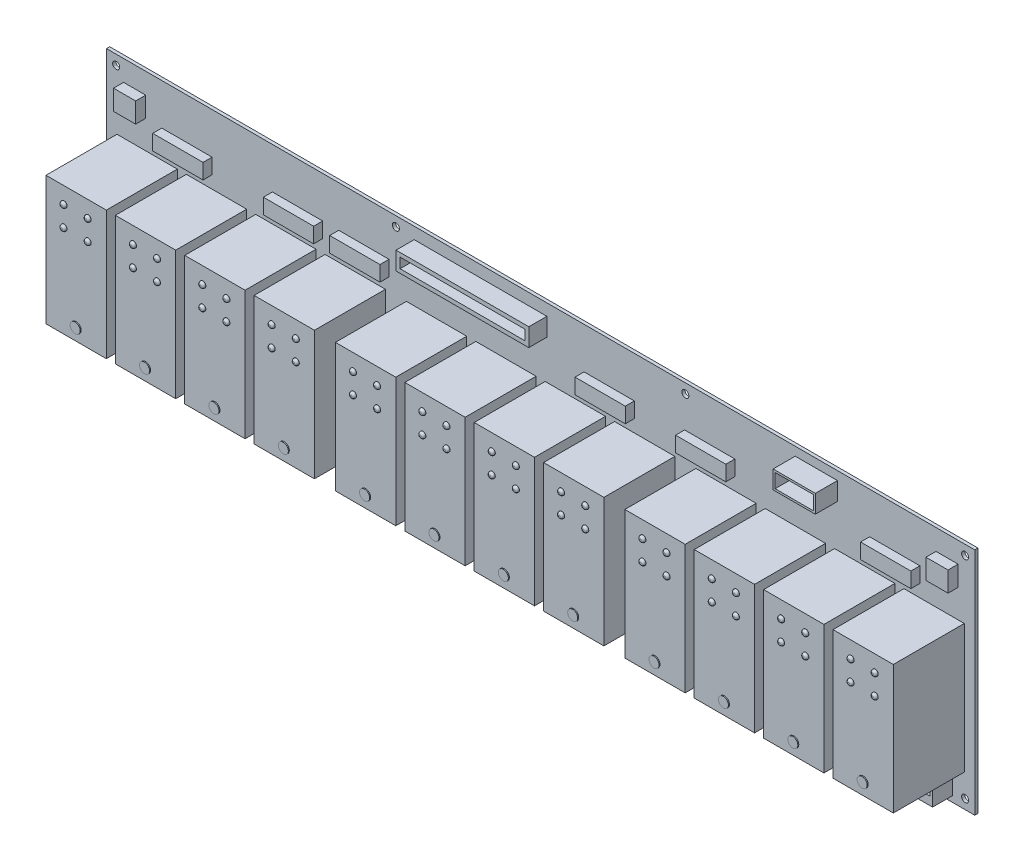
SolidWorks part; units mm, degrees
ref_plane "Front Plane" through (0, 0, 0) normal (0, 0, 1) x (1, 0, 0)
ref_plane "Top Plane" through (0, 0, 0) normal (0, 1, 0) x (1, 0, 0)
ref_plane "Right Plane" through (0, 0, 0) normal (1, 0, 0) x (0, 0, -1)
sketch "Sketch1" plane through (0, 0, 0) normal (0, 0, 1) x (1, 0, 0)
  line L1 (0, 0) -> (431.8, 0)
  line L2 (0, 0) -> (0, 114.3)
  line L3 (0, 114.3) -> (431.8, 114.3)
  line L4 (431.8, 0) -> (431.8, 114.3)
extrude "PCB" add sketch "Sketch1" along normal blind 1.6
ref_plane "Plane_z1_6" through (0, 0, 1.6) normal (0, 0, 1) x (1, 0, 0)
sketch "Sketch2" plane through (0, 0, 1.6) normal (0, 0, 1) x (1, 0, 0)
  line L1 (27.5, 86.2) -> (52.5, 86.2)
  line L2 (27.5, 86.2) -> (27.5, 93.8)
  line L3 (27.5, 93.8) -> (52.5, 93.8)
  line L4 (52.5, 86.2) -> (52.5, 93.8)
  line L6 (82.5, 86.2) -> (107.5, 86.2)
  line L7 (82.5, 86.2) -> (82.5, 93.8)
  line L8 (82.5, 93.8) -> (107.5, 93.8)
  line L9 (107.5, 86.2) -> (107.5, 93.8)
  line L11 (115.5, 86.2) -> (140.5, 86.2)
  line L12 (115.5, 86.2) -> (115.5, 93.8)
  line L13 (115.5, 93.8) -> (140.5, 93.8)
  line L14 (140.5, 86.2) -> (140.5, 93.8)
  line L16 (237.5, 86.2) -> (262.5, 86.2)
  line L17 (237.5, 86.2) -> (237.5, 93.8)
  line L18 (237.5, 93.8) -> (262.5, 93.8)
  line L19 (262.5, 86.2) -> (262.5, 93.8)
  line L21 (287.5, 86.2) -> (312.5, 86.2)
  line L22 (287.5, 86.2) -> (287.5, 93.8)
  line L23 (287.5, 93.8) -> (312.5, 93.8)
  line L24 (312.5, 86.2) -> (312.5, 93.8)
  line L26 (379.5, 86.2) -> (404.5, 86.2)
  line L27 (379.5, 86.2) -> (379.5, 93.8)
  line L28 (379.5, 93.8) -> (404.5, 93.8)
  line L29 (404.5, 86.2) -> (404.5, 93.8)
extrude "Body00" add sketch "Sketch2" along normal blind 4.5
sketch "Sketch3" plane through (0, 0, 1.6) normal (0, 0, 1) x (1, 0, 0)
  line L1 (8.5, 94) -> (19.5, 94)
  line L2 (8.5, 94) -> (8.5, 104)
  line L3 (8.5, 104) -> (19.5, 104)
  line L4 (19.5, 94) -> (19.5, 104)
  line L6 (412.5, 94) -> (423.5, 94)
  line L7 (412.5, 94) -> (412.5, 104)
  line L8 (412.5, 104) -> (423.5, 104)
  line L9 (423.5, 94) -> (423.5, 104)
extrude "Body01" add sketch "Sketch3" along normal blind 5
sketch "Sketch4" plane through (0, 0, 1.6) normal (0, 0, 1) x (1, 0, 0)
  line L1 (153, 99.5) -> (219, 99.5)
  line L2 (153, 99.5) -> (153, 108.5)
  line L3 (153, 108.5) -> (219, 108.5)
  line L4 (219, 99.5) -> (219, 108.5)
extrude "Body02" add sketch "Sketch4" along normal blind 9
sketch "Sketch5" plane through (0, 0, 1.6) normal (0, 0, 1) x (1, 0, 0)
  line L1 (11.007, 3) -> (132.927, 3)
  line L2 (11.007, 3) -> (11.007, 12)
  line L3 (11.007, 12) -> (132.927, 12)
  line L4 (132.927, 3) -> (132.927, 12)
  line L6 (154.94, 3) -> (276.86, 3)
  line L7 (154.94, 3) -> (154.94, 12)
  line L8 (154.94, 12) -> (276.86, 12)
  line L9 (276.86, 3) -> (276.86, 12)
  line L11 (298.873, 3) -> (420.793, 3)
  line L12 (298.873, 3) -> (298.873, 12)
  line L13 (298.873, 12) -> (420.793, 12)
  line L14 (420.793, 3) -> (420.793, 12)
extrude "Body03" add sketch "Sketch5" along normal blind 10
sketch "Sketch6" plane through (0, 0, 1.6) normal (0, 0, 1) x (1, 0, 0)
  line L1 (342.5, 101) -> (363.5, 101)
  line L2 (342.5, 101) -> (342.5, 110)
  line L3 (342.5, 110) -> (363.5, 110)
  line L4 (363.5, 101) -> (363.5, 110)
extrude "Body04" add sketch "Sketch6" along normal blind 11
sketch "Sketch7" plane through (0, 0, 1.6) normal (0, 0, 1) x (1, 0, 0)
  line L1 (5.217, 16) -> (35.217, 16)
  line L2 (5.217, 16) -> (5.217, 80)
  line L3 (5.217, 80) -> (35.217, 80)
  line L4 (35.217, 16) -> (35.217, 80)
  line L6 (39.717, 16) -> (69.717, 16)
  line L7 (39.717, 16) -> (39.717, 80)
  line L8 (39.717, 80) -> (69.717, 80)
  line L9 (69.717, 16) -> (69.717, 80)
  line L11 (74.217, 16) -> (104.217, 16)
  line L12 (74.217, 16) -> (74.217, 80)
  line L13 (74.217, 80) -> (104.217, 80)
  line L14 (104.217, 16) -> (104.217, 80)
  line L16 (108.717, 16) -> (138.717, 16)
  line L17 (108.717, 16) -> (108.717, 80)
  line L18 (108.717, 80) -> (138.717, 80)
  line L19 (138.717, 16) -> (138.717, 80)
  line L21 (149.15, 16) -> (179.15, 16)
  line L22 (149.15, 16) -> (149.15, 80)
  line L23 (149.15, 80) -> (179.15, 80)
  line L24 (179.15, 16) -> (179.15, 80)
  line L26 (183.65, 16) -> (213.65, 16)
  line L27 (183.65, 16) -> (183.65, 80)
  line L28 (183.65, 80) -> (213.65, 80)
  line L29 (213.65, 16) -> (213.65, 80)
  line L31 (218.15, 16) -> (248.15, 16)
  line L32 (218.15, 16) -> (218.15, 80)
  line L33 (218.15, 80) -> (248.15, 80)
  line L34 (248.15, 16) -> (248.15, 80)
  line L36 (252.65, 16) -> (282.65, 16)
  line L37 (252.65, 16) -> (252.65, 80)
  line L38 (252.65, 80) -> (282.65, 80)
  line L39 (282.65, 16) -> (282.65, 80)
  line L41 (293.083, 16) -> (323.083, 16)
  line L42 (293.083, 16) -> (293.083, 80)
  line L43 (293.083, 80) -> (323.083, 80)
  line L44 (323.083, 16) -> (323.083, 80)
  line L46 (327.583, 16) -> (357.583, 16)
  line L47 (327.583, 16) -> (327.583, 80)
  line L48 (327.583, 80) -> (357.583, 80)
  line L49 (357.583, 16) -> (357.583, 80)
  line L51 (362.083, 16) -> (392.083, 16)
  line L52 (362.083, 16) -> (362.083, 80)
  line L53 (362.083, 80) -> (392.083, 80)
  line L54 (392.083, 16) -> (392.083, 80)
  line L56 (396.583, 16) -> (426.583, 16)
  line L57 (396.583, 16) -> (396.583, 80)
  line L58 (396.583, 80) -> (426.583, 80)
  line L59 (426.583, 16) -> (426.583, 80)
extrude "Body05" add sketch "Sketch7" along normal blind 35.3
ref_plane "Plane_z36_9" through (0, 0, 36.9) normal (0, 0, 1) x (1, 0, 0)
sketch "Sketch8" plane through (0, 0, 36.9) normal (0, 0, 1) x (1, 0, 0)
  circle A0 centre (20.217, 22) radius 2.5
  circle A1 centre (54.717, 22) radius 2.5
  circle A2 centre (89.217, 22) radius 2.5
  circle A3 centre (123.717, 22) radius 2.5
  circle A4 centre (164.15, 22) radius 2.5
  circle A5 centre (198.65, 22) radius 2.5
  circle A6 centre (233.15, 22) radius 2.5
  circle A7 centre (267.65, 22) radius 2.5
  circle A8 centre (308.083, 22) radius 2.5
  circle A9 centre (342.583, 22) radius 2.5
  circle A10 centre (377.083, 22) radius 2.5
  circle A11 centre (411.583, 22) radius 2.5
extrude "Body06" add sketch "Sketch8" along normal blind 0.5
sketch "Sketch9" plane through (0, 0, 36.9) normal (0, 0, 1) x (1, 0, 0)
  circle A0 centre (14.217, 62) radius 1.5
  circle A1 centre (14.217, 72) radius 1.5
  circle A2 centre (26.217, 62) radius 1.5
  circle A3 centre (26.217, 72) radius 1.5
  circle A4 centre (48.717, 62) radius 1.5
  circle A5 centre (48.717, 72) radius 1.5
  circle A6 centre (60.717, 62) radius 1.5
  circle A7 centre (60.717, 72) radius 1.5
  circle A8 centre (83.217, 62) radius 1.5
  circle A9 centre (83.217, 72) radius 1.5
  circle A10 centre (95.217, 62) radius 1.5
  circle A11 centre (95.217, 72) radius 1.5
  circle A12 centre (117.717, 62) radius 1.5
  circle A13 centre (117.717, 72) radius 1.5
  circle A14 centre (129.717, 62) radius 1.5
  circle A15 centre (129.717, 72) radius 1.5
  circle A16 centre (158.15, 62) radius 1.5
  circle A17 centre (158.15, 72) radius 1.5
  circle A18 centre (170.15, 62) radius 1.5
  circle A19 centre (170.15, 72) radius 1.5
  circle A20 centre (192.65, 62) radius 1.5
  circle A21 centre (192.65, 72) radius 1.5
  circle A22 centre (204.65, 62) radius 1.5
  circle A23 centre (204.65, 72) radius 1.5
  circle A24 centre (227.15, 62) radius 1.5
  circle A25 centre (227.15, 72) radius 1.5
  circle A26 centre (239.15, 62) radius 1.5
  circle A27 centre (239.15, 72) radius 1.5
  circle A28 centre (261.65, 62) radius 1.5
  circle A29 centre (261.65, 72) radius 1.5
  circle A30 centre (273.65, 62) radius 1.5
  circle A31 centre (273.65, 72) radius 1.5
  circle A32 centre (302.083, 62) radius 1.5
  circle A33 centre (302.083, 72) radius 1.5
  circle A34 centre (314.083, 62) radius 1.5
  circle A35 centre (314.083, 72) radius 1.5
  circle A36 centre (336.583, 62) radius 1.5
  circle A37 centre (336.583, 72) radius 1.5
  circle A38 centre (348.583, 62) radius 1.5
  circle A39 centre (348.583, 72) radius 1.5
  circle A40 centre (371.083, 62) radius 1.5
  circle A41 centre (371.083, 72) radius 1.5
  circle A42 centre (383.083, 62) radius 1.5
  circle A43 centre (383.083, 72) radius 1.5
  circle A44 centre (405.583, 62) radius 1.5
  circle A45 centre (405.583, 72) radius 1.5
  circle A46 centre (417.583, 62) radius 1.5
  circle A47 centre (417.583, 72) radius 1.5
extrude "Body07" add sketch "Sketch9" along normal blind 1.2
ref_plane "Plane_y7" through (0, 7, 0) normal (0, 1, 0) x (1, 0, 0)
sketch "Sketch10" plane through (0, 7, 0) normal (0, 1, 0) x (1, 0, 0)
  line L1 (11.947, -3.5) -> (15.147, -3.5)
  line L2 (11.947, -3.5) -> (11.947, -6.7)
  line L3 (11.947, -6.7) -> (15.147, -6.7)
  line L4 (15.147, -3.5) -> (15.147, -6.7)
  line L6 (17.027, -3.5) -> (20.227, -3.5)
  line L7 (17.027, -3.5) -> (17.027, -6.7)
  line L8 (17.027, -6.7) -> (20.227, -6.7)
  line L9 (20.227, -3.5) -> (20.227, -6.7)
  line L11 (22.107, -3.5) -> (25.307, -3.5)
  line L12 (22.107, -3.5) -> (22.107, -6.7)
  line L13 (22.107, -6.7) -> (25.307, -6.7)
  line L14 (25.307, -3.5) -> (25.307, -6.7)
  line L16 (27.187, -3.5) -> (30.387, -3.5)
  line L17 (27.187, -3.5) -> (27.187, -6.7)
  line L18 (27.187, -6.7) -> (30.387, -6.7)
  line L19 (30.387, -3.5) -> (30.387, -6.7)
  line L21 (32.267, -3.5) -> (35.467, -3.5)
  line L22 (32.267, -3.5) -> (32.267, -6.7)
  line L23 (32.267, -6.7) -> (35.467, -6.7)
  line L24 (35.467, -3.5) -> (35.467, -6.7)
  line L26 (37.347, -3.5) -> (40.547, -3.5)
  line L27 (37.347, -3.5) -> (37.347, -6.7)
  line L28 (37.347, -6.7) -> (40.547, -6.7)
  line L29 (40.547, -3.5) -> (40.547, -6.7)
  line L31 (42.427, -3.5) -> (45.627, -3.5)
  line L32 (42.427, -3.5) -> (42.427, -6.7)
  line L33 (42.427, -6.7) -> (45.627, -6.7)
  line L34 (45.627, -3.5) -> (45.627, -6.7)
  line L36 (47.507, -3.5) -> (50.707, -3.5)
  line L37 (47.507, -3.5) -> (47.507, -6.7)
  line L38 (47.507, -6.7) -> (50.707, -6.7)
  line L39 (50.707, -3.5) -> (50.707, -6.7)
  line L41 (52.587, -3.5) -> (55.787, -3.5)
  line L42 (52.587, -3.5) -> (52.587, -6.7)
  line L43 (52.587, -6.7) -> (55.787, -6.7)
  line L44 (55.787, -3.5) -> (55.787, -6.7)
  line L46 (57.667, -3.5) -> (60.867, -3.5)
  line L47 (57.667, -3.5) -> (57.667, -6.7)
  line L48 (57.667, -6.7) -> (60.867, -6.7)
  line L49 (60.867, -3.5) -> (60.867, -6.7)
  line L51 (62.747, -3.5) -> (65.947, -3.5)
  line L52 (62.747, -3.5) -> (62.747, -6.7)
  line L53 (62.747, -6.7) -> (65.947, -6.7)
  line L54 (65.947, -3.5) -> (65.947, -6.7)
  line L56 (67.827, -3.5) -> (71.027, -3.5)
  line L57 (67.827, -3.5) -> (67.827, -6.7)
  line L58 (67.827, -6.7) -> (71.027, -6.7)
  line L59 (71.027, -3.5) -> (71.027, -6.7)
  line L61 (72.907, -3.5) -> (76.107, -3.5)
  line L62 (72.907, -3.5) -> (72.907, -6.7)
  line L63 (72.907, -6.7) -> (76.107, -6.7)
  line L64 (76.107, -3.5) -> (76.107, -6.7)
  line L66 (77.987, -3.5) -> (81.187, -3.5)
  line L67 (77.987, -3.5) -> (77.987, -6.7)
  line L68 (77.987, -6.7) -> (81.187, -6.7)
  line L69 (81.187, -3.5) -> (81.187, -6.7)
  line L71 (83.067, -3.5) -> (86.267, -3.5)
  line L72 (83.067, -3.5) -> (83.067, -6.7)
  line L73 (83.067, -6.7) -> (86.267, -6.7)
  line L74 (86.267, -3.5) -> (86.267, -6.7)
  line L76 (88.147, -3.5) -> (91.347, -3.5)
  line L77 (88.147, -3.5) -> (88.147, -6.7)
  line L78 (88.147, -6.7) -> (91.347, -6.7)
  line L79 (91.347, -3.5) -> (91.347, -6.7)
  line L81 (93.227, -3.5) -> (96.427, -3.5)
  line L82 (93.227, -3.5) -> (93.227, -6.7)
  line L83 (93.227, -6.7) -> (96.427, -6.7)
  line L84 (96.427, -3.5) -> (96.427, -6.7)
  line L86 (98.307, -3.5) -> (101.507, -3.5)
  line L87 (98.307, -3.5) -> (98.307, -6.7)
  line L88 (98.307, -6.7) -> (101.507, -6.7)
  line L89 (101.507, -3.5) -> (101.507, -6.7)
  line L91 (103.387, -3.5) -> (106.587, -3.5)
  line L92 (103.387, -3.5) -> (103.387, -6.7)
  line L93 (103.387, -6.7) -> (106.587, -6.7)
  line L94 (106.587, -3.5) -> (106.587, -6.7)
  line L96 (108.467, -3.5) -> (111.667, -3.5)
  line L97 (108.467, -3.5) -> (108.467, -6.7)
  line L98 (108.467, -6.7) -> (111.667, -6.7)
  line L99 (111.667, -3.5) -> (111.667, -6.7)
  line L101 (113.547, -3.5) -> (116.747, -3.5)
  line L102 (113.547, -3.5) -> (113.547, -6.7)
  line L103 (113.547, -6.7) -> (116.747, -6.7)
  line L104 (116.747, -3.5) -> (116.747, -6.7)
  line L106 (118.627, -3.5) -> (121.827, -3.5)
  line L107 (118.627, -3.5) -> (118.627, -6.7)
  line L108 (118.627, -6.7) -> (121.827, -6.7)
  line L109 (121.827, -3.5) -> (121.827, -6.7)
  line L111 (123.707, -3.5) -> (126.907, -3.5)
  line L112 (123.707, -3.5) -> (123.707, -6.7)
  line L113 (123.707, -6.7) -> (126.907, -6.7)
  line L114 (126.907, -3.5) -> (126.907, -6.7)
  line L116 (128.787, -3.5) -> (131.987, -3.5)
  line L117 (128.787, -3.5) -> (128.787, -6.7)
  line L118 (128.787, -6.7) -> (131.987, -6.7)
  line L119 (131.987, -3.5) -> (131.987, -6.7)
  line L121 (155.88, -3.5) -> (159.08, -3.5)
  line L122 (155.88, -3.5) -> (155.88, -6.7)
  line L123 (155.88, -6.7) -> (159.08, -6.7)
  line L124 (159.08, -3.5) -> (159.08, -6.7)
  line L126 (160.96, -3.5) -> (164.16, -3.5)
  line L127 (160.96, -3.5) -> (160.96, -6.7)
  line L128 (160.96, -6.7) -> (164.16, -6.7)
  line L129 (164.16, -3.5) -> (164.16, -6.7)
  line L131 (166.04, -3.5) -> (169.24, -3.5)
  line L132 (166.04, -3.5) -> (166.04, -6.7)
  line L133 (166.04, -6.7) -> (169.24, -6.7)
  line L134 (169.24, -3.5) -> (169.24, -6.7)
  line L136 (171.12, -3.5) -> (174.32, -3.5)
  line L137 (171.12, -3.5) -> (171.12, -6.7)
  line L138 (171.12, -6.7) -> (174.32, -6.7)
  line L139 (174.32, -3.5) -> (174.32, -6.7)
  line L141 (176.2, -3.5) -> (179.4, -3.5)
  line L142 (176.2, -3.5) -> (176.2, -6.7)
  line L143 (176.2, -6.7) -> (179.4, -6.7)
  line L144 (179.4, -3.5) -> (179.4, -6.7)
  line L146 (181.28, -3.5) -> (184.48, -3.5)
  line L147 (181.28, -3.5) -> (181.28, -6.7)
  line L148 (181.28, -6.7) -> (184.48, -6.7)
  line L149 (184.48, -3.5) -> (184.48, -6.7)
  line L151 (186.36, -3.5) -> (189.56, -3.5)
  line L152 (186.36, -3.5) -> (186.36, -6.7)
  line L153 (186.36, -6.7) -> (189.56, -6.7)
  line L154 (189.56, -3.5) -> (189.56, -6.7)
  line L156 (191.44, -3.5) -> (194.64, -3.5)
  line L157 (191.44, -3.5) -> (191.44, -6.7)
  line L158 (191.44, -6.7) -> (194.64, -6.7)
  line L159 (194.64, -3.5) -> (194.64, -6.7)
  line L161 (196.52, -3.5) -> (199.72, -3.5)
  line L162 (196.52, -3.5) -> (196.52, -6.7)
  line L163 (196.52, -6.7) -> (199.72, -6.7)
  line L164 (199.72, -3.5) -> (199.72, -6.7)
  line L166 (201.6, -3.5) -> (204.8, -3.5)
  line L167 (201.6, -3.5) -> (201.6, -6.7)
  line L168 (201.6, -6.7) -> (204.8, -6.7)
  line L169 (204.8, -3.5) -> (204.8, -6.7)
  line L171 (206.68, -3.5) -> (209.88, -3.5)
  line L172 (206.68, -3.5) -> (206.68, -6.7)
  line L173 (206.68, -6.7) -> (209.88, -6.7)
  line L174 (209.88, -3.5) -> (209.88, -6.7)
  line L176 (211.76, -3.5) -> (214.96, -3.5)
  line L177 (211.76, -3.5) -> (211.76, -6.7)
  line L178 (211.76, -6.7) -> (214.96, -6.7)
  line L179 (214.96, -3.5) -> (214.96, -6.7)
  line L181 (216.84, -3.5) -> (220.04, -3.5)
  line L182 (216.84, -3.5) -> (216.84, -6.7)
  line L183 (216.84, -6.7) -> (220.04, -6.7)
  line L184 (220.04, -3.5) -> (220.04, -6.7)
  line L186 (221.92, -3.5) -> (225.12, -3.5)
  line L187 (221.92, -3.5) -> (221.92, -6.7)
  line L188 (221.92, -6.7) -> (225.12, -6.7)
  line L189 (225.12, -3.5) -> (225.12, -6.7)
  line L191 (227, -3.5) -> (230.2, -3.5)
  line L192 (227, -3.5) -> (227, -6.7)
  line L193 (227, -6.7) -> (230.2, -6.7)
  line L194 (230.2, -3.5) -> (230.2, -6.7)
  line L196 (232.08, -3.5) -> (235.28, -3.5)
  line L197 (232.08, -3.5) -> (232.08, -6.7)
  line L198 (232.08, -6.7) -> (235.28, -6.7)
  line L199 (235.28, -3.5) -> (235.28, -6.7)
  line L201 (237.16, -3.5) -> (240.36, -3.5)
  line L202 (237.16, -3.5) -> (237.16, -6.7)
  line L203 (237.16, -6.7) -> (240.36, -6.7)
  line L204 (240.36, -3.5) -> (240.36, -6.7)
  line L206 (242.24, -3.5) -> (245.44, -3.5)
  line L207 (242.24, -3.5) -> (242.24, -6.7)
  line L208 (242.24, -6.7) -> (245.44, -6.7)
  line L209 (245.44, -3.5) -> (245.44, -6.7)
  line L211 (247.32, -3.5) -> (250.52, -3.5)
  line L212 (247.32, -3.5) -> (247.32, -6.7)
  line L213 (247.32, -6.7) -> (250.52, -6.7)
  line L214 (250.52, -3.5) -> (250.52, -6.7)
  line L216 (252.4, -3.5) -> (255.6, -3.5)
  line L217 (252.4, -3.5) -> (252.4, -6.7)
  line L218 (252.4, -6.7) -> (255.6, -6.7)
  line L219 (255.6, -3.5) -> (255.6, -6.7)
  line L221 (257.48, -3.5) -> (260.68, -3.5)
  line L222 (257.48, -3.5) -> (257.48, -6.7)
  line L223 (257.48, -6.7) -> (260.68, -6.7)
  line L224 (260.68, -3.5) -> (260.68, -6.7)
  line L226 (262.56, -3.5) -> (265.76, -3.5)
  line L227 (262.56, -3.5) -> (262.56, -6.7)
  line L228 (262.56, -6.7) -> (265.76, -6.7)
  line L229 (265.76, -3.5) -> (265.76, -6.7)
  line L231 (267.64, -3.5) -> (270.84, -3.5)
  line L232 (267.64, -3.5) -> (267.64, -6.7)
  line L233 (267.64, -6.7) -> (270.84, -6.7)
  line L234 (270.84, -3.5) -> (270.84, -6.7)
  line L236 (272.72, -3.5) -> (275.92, -3.5)
  line L237 (272.72, -3.5) -> (272.72, -6.7)
  line L238 (272.72, -6.7) -> (275.92, -6.7)
  line L239 (275.92, -3.5) -> (275.92, -6.7)
  line L241 (299.813, -3.5) -> (303.013, -3.5)
  line L242 (299.813, -3.5) -> (299.813, -6.7)
  line L243 (299.813, -6.7) -> (303.013, -6.7)
  line L244 (303.013, -3.5) -> (303.013, -6.7)
  line L246 (304.893, -3.5) -> (308.093, -3.5)
  line L247 (304.893, -3.5) -> (304.893, -6.7)
  line L248 (304.893, -6.7) -> (308.093, -6.7)
  line L249 (308.093, -3.5) -> (308.093, -6.7)
  line L251 (309.973, -3.5) -> (313.173, -3.5)
  line L252 (309.973, -3.5) -> (309.973, -6.7)
  line L253 (309.973, -6.7) -> (313.173, -6.7)
  line L254 (313.173, -3.5) -> (313.173, -6.7)
  line L256 (315.053, -3.5) -> (318.253, -3.5)
  line L257 (315.053, -3.5) -> (315.053, -6.7)
  line L258 (315.053, -6.7) -> (318.253, -6.7)
  line L259 (318.253, -3.5) -> (318.253, -6.7)
  line L261 (320.133, -3.5) -> (323.333, -3.5)
  line L262 (320.133, -3.5) -> (320.133, -6.7)
  line L263 (320.133, -6.7) -> (323.333, -6.7)
  line L264 (323.333, -3.5) -> (323.333, -6.7)
  line L266 (325.213, -3.5) -> (328.413, -3.5)
  line L267 (325.213, -3.5) -> (325.213, -6.7)
  line L268 (325.213, -6.7) -> (328.413, -6.7)
  line L269 (328.413, -3.5) -> (328.413, -6.7)
  line L271 (330.293, -3.5) -> (333.493, -3.5)
  line L272 (330.293, -3.5) -> (330.293, -6.7)
  line L273 (330.293, -6.7) -> (333.493, -6.7)
  line L274 (333.493, -3.5) -> (333.493, -6.7)
  line L276 (335.373, -3.5) -> (338.573, -3.5)
  line L277 (335.373, -3.5) -> (335.373, -6.7)
  line L278 (335.373, -6.7) -> (338.573, -6.7)
  line L279 (338.573, -3.5) -> (338.573, -6.7)
  line L281 (340.453, -3.5) -> (343.653, -3.5)
  line L282 (340.453, -3.5) -> (340.453, -6.7)
  line L283 (340.453, -6.7) -> (343.653, -6.7)
  line L284 (343.653, -3.5) -> (343.653, -6.7)
  line L286 (345.533, -3.5) -> (348.733, -3.5)
  line L287 (345.533, -3.5) -> (345.533, -6.7)
  line L288 (345.533, -6.7) -> (348.733, -6.7)
  line L289 (348.733, -3.5) -> (348.733, -6.7)
  line L291 (350.613, -3.5) -> (353.813, -3.5)
  line L292 (350.613, -3.5) -> (350.613, -6.7)
  line L293 (350.613, -6.7) -> (353.813, -6.7)
  line L294 (353.813, -3.5) -> (353.813, -6.7)
  line L296 (355.693, -3.5) -> (358.893, -3.5)
  line L297 (355.693, -3.5) -> (355.693, -6.7)
  line L298 (355.693, -6.7) -> (358.893, -6.7)
  line L299 (358.893, -3.5) -> (358.893, -6.7)
  line L301 (360.773, -3.5) -> (363.973, -3.5)
  line L302 (360.773, -3.5) -> (360.773, -6.7)
  line L303 (360.773, -6.7) -> (363.973, -6.7)
  line L304 (363.973, -3.5) -> (363.973, -6.7)
  line L306 (365.853, -3.5) -> (369.053, -3.5)
  line L307 (365.853, -3.5) -> (365.853, -6.7)
  line L308 (365.853, -6.7) -> (369.053, -6.7)
  line L309 (369.053, -3.5) -> (369.053, -6.7)
  line L311 (370.933, -3.5) -> (374.133, -3.5)
  line L312 (370.933, -3.5) -> (370.933, -6.7)
  line L313 (370.933, -6.7) -> (374.133, -6.7)
  line L314 (374.133, -3.5) -> (374.133, -6.7)
  line L316 (376.013, -3.5) -> (379.213, -3.5)
  line L317 (376.013, -3.5) -> (376.013, -6.7)
  line L318 (376.013, -6.7) -> (379.213, -6.7)
  line L319 (379.213, -3.5) -> (379.213, -6.7)
  line L321 (381.093, -3.5) -> (384.293, -3.5)
  line L322 (381.093, -3.5) -> (381.093, -6.7)
  line L323 (381.093, -6.7) -> (384.293, -6.7)
  line L324 (384.293, -3.5) -> (384.293, -6.7)
  line L326 (386.173, -3.5) -> (389.373, -3.5)
  line L327 (386.173, -3.5) -> (386.173, -6.7)
  line L328 (386.173, -6.7) -> (389.373, -6.7)
  line L329 (389.373, -3.5) -> (389.373, -6.7)
  line L331 (391.253, -3.5) -> (394.453, -3.5)
  line L332 (391.253, -3.5) -> (391.253, -6.7)
  line L333 (391.253, -6.7) -> (394.453, -6.7)
  line L334 (394.453, -3.5) -> (394.453, -6.7)
  line L336 (396.333, -3.5) -> (399.533, -3.5)
  line L337 (396.333, -3.5) -> (396.333, -6.7)
  line L338 (396.333, -6.7) -> (399.533, -6.7)
  line L339 (399.533, -3.5) -> (399.533, -6.7)
  line L341 (401.413, -3.5) -> (404.613, -3.5)
  line L342 (401.413, -3.5) -> (401.413, -6.7)
  line L343 (401.413, -6.7) -> (404.613, -6.7)
  line L344 (404.613, -3.5) -> (404.613, -6.7)
  line L346 (406.493, -3.5) -> (409.693, -3.5)
  line L347 (406.493, -3.5) -> (406.493, -6.7)
  line L348 (406.493, -6.7) -> (409.693, -6.7)
  line L349 (409.693, -3.5) -> (409.693, -6.7)
  line L351 (411.573, -3.5) -> (414.773, -3.5)
  line L352 (411.573, -3.5) -> (411.573, -6.7)
  line L353 (411.573, -6.7) -> (414.773, -6.7)
  line L354 (414.773, -3.5) -> (414.773, -6.7)
  line L356 (416.653, -3.5) -> (419.853, -3.5)
  line L357 (416.653, -3.5) -> (416.653, -6.7)
  line L358 (416.653, -6.7) -> (419.853, -6.7)
  line L359 (419.853, -3.5) -> (419.853, -6.7)
extrude "Cut00" cut sketch "Sketch10" against normal blind 4
ref_plane "Plane_z10_6" through (0, 0, 10.6) normal (0, 0, 1) x (1, 0, 0)
sketch "Sketch11" plane through (0, 0, 10.6) normal (0, 0, 1) x (1, 0, 0)
  line L1 (155, 101.5) -> (217, 101.5)
  line L2 (155, 101.5) -> (155, 106.5)
  line L3 (155, 106.5) -> (217, 106.5)
  line L4 (217, 101.5) -> (217, 106.5)
extrude "Cut01" cut sketch "Sketch11" against normal blind 7
ref_plane "Plane_z11_6" through (0, 0, 11.6) normal (0, 0, 1) x (1, 0, 0)
sketch "Sketch12" plane through (0, 0, 11.6) normal (0, 0, 1) x (1, 0, 0)
  line L1 (12.147, 7.1) -> (14.947, 7.1)
  line L2 (12.147, 7.1) -> (12.147, 9.9)
  line L3 (12.147, 9.9) -> (14.947, 9.9)
  line L4 (14.947, 7.1) -> (14.947, 9.9)
  line L6 (17.227, 7.1) -> (20.027, 7.1)
  line L7 (17.227, 7.1) -> (17.227, 9.9)
  line L8 (17.227, 9.9) -> (20.027, 9.9)
  line L9 (20.027, 7.1) -> (20.027, 9.9)
  line L11 (22.307, 7.1) -> (25.107, 7.1)
  line L12 (22.307, 7.1) -> (22.307, 9.9)
  line L13 (22.307, 9.9) -> (25.107, 9.9)
  line L14 (25.107, 7.1) -> (25.107, 9.9)
  line L16 (27.387, 7.1) -> (30.187, 7.1)
  line L17 (27.387, 7.1) -> (27.387, 9.9)
  line L18 (27.387, 9.9) -> (30.187, 9.9)
  line L19 (30.187, 7.1) -> (30.187, 9.9)
  line L21 (32.467, 7.1) -> (35.267, 7.1)
  line L22 (32.467, 7.1) -> (32.467, 9.9)
  line L23 (32.467, 9.9) -> (35.267, 9.9)
  line L24 (35.267, 7.1) -> (35.267, 9.9)
  line L26 (37.547, 7.1) -> (40.347, 7.1)
  line L27 (37.547, 7.1) -> (37.547, 9.9)
  line L28 (37.547, 9.9) -> (40.347, 9.9)
  line L29 (40.347, 7.1) -> (40.347, 9.9)
  line L31 (42.627, 7.1) -> (45.427, 7.1)
  line L32 (42.627, 7.1) -> (42.627, 9.9)
  line L33 (42.627, 9.9) -> (45.427, 9.9)
  line L34 (45.427, 7.1) -> (45.427, 9.9)
  line L36 (47.707, 7.1) -> (50.507, 7.1)
  line L37 (47.707, 7.1) -> (47.707, 9.9)
  line L38 (47.707, 9.9) -> (50.507, 9.9)
  line L39 (50.507, 7.1) -> (50.507, 9.9)
  line L41 (52.787, 7.1) -> (55.587, 7.1)
  line L42 (52.787, 7.1) -> (52.787, 9.9)
  line L43 (52.787, 9.9) -> (55.587, 9.9)
  line L44 (55.587, 7.1) -> (55.587, 9.9)
  line L46 (57.867, 7.1) -> (60.667, 7.1)
  line L47 (57.867, 7.1) -> (57.867, 9.9)
  line L48 (57.867, 9.9) -> (60.667, 9.9)
  line L49 (60.667, 7.1) -> (60.667, 9.9)
  line L51 (62.947, 7.1) -> (65.747, 7.1)
  line L52 (62.947, 7.1) -> (62.947, 9.9)
  line L53 (62.947, 9.9) -> (65.747, 9.9)
  line L54 (65.747, 7.1) -> (65.747, 9.9)
  line L56 (68.027, 7.1) -> (70.827, 7.1)
  line L57 (68.027, 7.1) -> (68.027, 9.9)
  line L58 (68.027, 9.9) -> (70.827, 9.9)
  line L59 (70.827, 7.1) -> (70.827, 9.9)
  line L61 (73.107, 7.1) -> (75.907, 7.1)
  line L62 (73.107, 7.1) -> (73.107, 9.9)
  line L63 (73.107, 9.9) -> (75.907, 9.9)
  line L64 (75.907, 7.1) -> (75.907, 9.9)
  line L66 (78.187, 7.1) -> (80.987, 7.1)
  line L67 (78.187, 7.1) -> (78.187, 9.9)
  line L68 (78.187, 9.9) -> (80.987, 9.9)
  line L69 (80.987, 7.1) -> (80.987, 9.9)
  line L71 (83.267, 7.1) -> (86.067, 7.1)
  line L72 (83.267, 7.1) -> (83.267, 9.9)
  line L73 (83.267, 9.9) -> (86.067, 9.9)
  line L74 (86.067, 7.1) -> (86.067, 9.9)
  line L76 (88.347, 7.1) -> (91.147, 7.1)
  line L77 (88.347, 7.1) -> (88.347, 9.9)
  line L78 (88.347, 9.9) -> (91.147, 9.9)
  line L79 (91.147, 7.1) -> (91.147, 9.9)
  line L81 (93.427, 7.1) -> (96.227, 7.1)
  line L82 (93.427, 7.1) -> (93.427, 9.9)
  line L83 (93.427, 9.9) -> (96.227, 9.9)
  line L84 (96.227, 7.1) -> (96.227, 9.9)
  line L86 (98.507, 7.1) -> (101.307, 7.1)
  line L87 (98.507, 7.1) -> (98.507, 9.9)
  line L88 (98.507, 9.9) -> (101.307, 9.9)
  line L89 (101.307, 7.1) -> (101.307, 9.9)
  line L91 (103.587, 7.1) -> (106.387, 7.1)
  line L92 (103.587, 7.1) -> (103.587, 9.9)
  line L93 (103.587, 9.9) -> (106.387, 9.9)
  line L94 (106.387, 7.1) -> (106.387, 9.9)
  line L96 (108.667, 7.1) -> (111.467, 7.1)
  line L97 (108.667, 7.1) -> (108.667, 9.9)
  line L98 (108.667, 9.9) -> (111.467, 9.9)
  line L99 (111.467, 7.1) -> (111.467, 9.9)
  line L101 (113.747, 7.1) -> (116.547, 7.1)
  line L102 (113.747, 7.1) -> (113.747, 9.9)
  line L103 (113.747, 9.9) -> (116.547, 9.9)
  line L104 (116.547, 7.1) -> (116.547, 9.9)
  line L106 (118.827, 7.1) -> (121.627, 7.1)
  line L107 (118.827, 7.1) -> (118.827, 9.9)
  line L108 (118.827, 9.9) -> (121.627, 9.9)
  line L109 (121.627, 7.1) -> (121.627, 9.9)
  line L111 (123.907, 7.1) -> (126.707, 7.1)
  line L112 (123.907, 7.1) -> (123.907, 9.9)
  line L113 (123.907, 9.9) -> (126.707, 9.9)
  line L114 (126.707, 7.1) -> (126.707, 9.9)
  line L116 (128.987, 7.1) -> (131.787, 7.1)
  line L117 (128.987, 7.1) -> (128.987, 9.9)
  line L118 (128.987, 9.9) -> (131.787, 9.9)
  line L119 (131.787, 7.1) -> (131.787, 9.9)
  line L121 (156.08, 7.1) -> (158.88, 7.1)
  line L122 (156.08, 7.1) -> (156.08, 9.9)
  line L123 (156.08, 9.9) -> (158.88, 9.9)
  line L124 (158.88, 7.1) -> (158.88, 9.9)
  line L126 (161.16, 7.1) -> (163.96, 7.1)
  line L127 (161.16, 7.1) -> (161.16, 9.9)
  line L128 (161.16, 9.9) -> (163.96, 9.9)
  line L129 (163.96, 7.1) -> (163.96, 9.9)
  line L131 (166.24, 7.1) -> (169.04, 7.1)
  line L132 (166.24, 7.1) -> (166.24, 9.9)
  line L133 (166.24, 9.9) -> (169.04, 9.9)
  line L134 (169.04, 7.1) -> (169.04, 9.9)
  line L136 (171.32, 7.1) -> (174.12, 7.1)
  line L137 (171.32, 7.1) -> (171.32, 9.9)
  line L138 (171.32, 9.9) -> (174.12, 9.9)
  line L139 (174.12, 7.1) -> (174.12, 9.9)
  line L141 (176.4, 7.1) -> (179.2, 7.1)
  line L142 (176.4, 7.1) -> (176.4, 9.9)
  line L143 (176.4, 9.9) -> (179.2, 9.9)
  line L144 (179.2, 7.1) -> (179.2, 9.9)
  line L146 (181.48, 7.1) -> (184.28, 7.1)
  line L147 (181.48, 7.1) -> (181.48, 9.9)
  line L148 (181.48, 9.9) -> (184.28, 9.9)
  line L149 (184.28, 7.1) -> (184.28, 9.9)
  line L151 (186.56, 7.1) -> (189.36, 7.1)
  line L152 (186.56, 7.1) -> (186.56, 9.9)
  line L153 (186.56, 9.9) -> (189.36, 9.9)
  line L154 (189.36, 7.1) -> (189.36, 9.9)
  line L156 (191.64, 7.1) -> (194.44, 7.1)
  line L157 (191.64, 7.1) -> (191.64, 9.9)
  line L158 (191.64, 9.9) -> (194.44, 9.9)
  line L159 (194.44, 7.1) -> (194.44, 9.9)
  line L161 (196.72, 7.1) -> (199.52, 7.1)
  line L162 (196.72, 7.1) -> (196.72, 9.9)
  line L163 (196.72, 9.9) -> (199.52, 9.9)
  line L164 (199.52, 7.1) -> (199.52, 9.9)
  line L166 (201.8, 7.1) -> (204.6, 7.1)
  line L167 (201.8, 7.1) -> (201.8, 9.9)
  line L168 (201.8, 9.9) -> (204.6, 9.9)
  line L169 (204.6, 7.1) -> (204.6, 9.9)
  line L171 (206.88, 7.1) -> (209.68, 7.1)
  line L172 (206.88, 7.1) -> (206.88, 9.9)
  line L173 (206.88, 9.9) -> (209.68, 9.9)
  line L174 (209.68, 7.1) -> (209.68, 9.9)
  line L176 (211.96, 7.1) -> (214.76, 7.1)
  line L177 (211.96, 7.1) -> (211.96, 9.9)
  line L178 (211.96, 9.9) -> (214.76, 9.9)
  line L179 (214.76, 7.1) -> (214.76, 9.9)
  line L181 (217.04, 7.1) -> (219.84, 7.1)
  line L182 (217.04, 7.1) -> (217.04, 9.9)
  line L183 (217.04, 9.9) -> (219.84, 9.9)
  line L184 (219.84, 7.1) -> (219.84, 9.9)
  line L186 (222.12, 7.1) -> (224.92, 7.1)
  line L187 (222.12, 7.1) -> (222.12, 9.9)
  line L188 (222.12, 9.9) -> (224.92, 9.9)
  line L189 (224.92, 7.1) -> (224.92, 9.9)
  line L191 (227.2, 7.1) -> (230, 7.1)
  line L192 (227.2, 7.1) -> (227.2, 9.9)
  line L193 (227.2, 9.9) -> (230, 9.9)
  line L194 (230, 7.1) -> (230, 9.9)
  line L196 (232.28, 7.1) -> (235.08, 7.1)
  line L197 (232.28, 7.1) -> (232.28, 9.9)
  line L198 (232.28, 9.9) -> (235.08, 9.9)
  line L199 (235.08, 7.1) -> (235.08, 9.9)
  line L201 (237.36, 7.1) -> (240.16, 7.1)
  line L202 (237.36, 7.1) -> (237.36, 9.9)
  line L203 (237.36, 9.9) -> (240.16, 9.9)
  line L204 (240.16, 7.1) -> (240.16, 9.9)
  line L206 (242.44, 7.1) -> (245.24, 7.1)
  line L207 (242.44, 7.1) -> (242.44, 9.9)
  line L208 (242.44, 9.9) -> (245.24, 9.9)
  line L209 (245.24, 7.1) -> (245.24, 9.9)
  line L211 (247.52, 7.1) -> (250.32, 7.1)
  line L212 (247.52, 7.1) -> (247.52, 9.9)
  line L213 (247.52, 9.9) -> (250.32, 9.9)
  line L214 (250.32, 7.1) -> (250.32, 9.9)
  line L216 (252.6, 7.1) -> (255.4, 7.1)
  line L217 (252.6, 7.1) -> (252.6, 9.9)
  line L218 (252.6, 9.9) -> (255.4, 9.9)
  line L219 (255.4, 7.1) -> (255.4, 9.9)
  line L221 (257.68, 7.1) -> (260.48, 7.1)
  line L222 (257.68, 7.1) -> (257.68, 9.9)
  line L223 (257.68, 9.9) -> (260.48, 9.9)
  line L224 (260.48, 7.1) -> (260.48, 9.9)
  line L226 (262.76, 7.1) -> (265.56, 7.1)
  line L227 (262.76, 7.1) -> (262.76, 9.9)
  line L228 (262.76, 9.9) -> (265.56, 9.9)
  line L229 (265.56, 7.1) -> (265.56, 9.9)
  line L231 (267.84, 7.1) -> (270.64, 7.1)
  line L232 (267.84, 7.1) -> (267.84, 9.9)
  line L233 (267.84, 9.9) -> (270.64, 9.9)
  line L234 (270.64, 7.1) -> (270.64, 9.9)
  line L236 (272.92, 7.1) -> (275.72, 7.1)
  line L237 (272.92, 7.1) -> (272.92, 9.9)
  line L238 (272.92, 9.9) -> (275.72, 9.9)
  line L239 (275.72, 7.1) -> (275.72, 9.9)
  line L241 (300.013, 7.1) -> (302.813, 7.1)
  line L242 (300.013, 7.1) -> (300.013, 9.9)
  line L243 (300.013, 9.9) -> (302.813, 9.9)
  line L244 (302.813, 7.1) -> (302.813, 9.9)
  line L246 (305.093, 7.1) -> (307.893, 7.1)
  line L247 (305.093, 7.1) -> (305.093, 9.9)
  line L248 (305.093, 9.9) -> (307.893, 9.9)
  line L249 (307.893, 7.1) -> (307.893, 9.9)
  line L251 (310.173, 7.1) -> (312.973, 7.1)
  line L252 (310.173, 7.1) -> (310.173, 9.9)
  line L253 (310.173, 9.9) -> (312.973, 9.9)
  line L254 (312.973, 7.1) -> (312.973, 9.9)
  line L256 (315.253, 7.1) -> (318.053, 7.1)
  line L257 (315.253, 7.1) -> (315.253, 9.9)
  line L258 (315.253, 9.9) -> (318.053, 9.9)
  line L259 (318.053, 7.1) -> (318.053, 9.9)
  line L261 (320.333, 7.1) -> (323.133, 7.1)
  line L262 (320.333, 7.1) -> (320.333, 9.9)
  line L263 (320.333, 9.9) -> (323.133, 9.9)
  line L264 (323.133, 7.1) -> (323.133, 9.9)
  line L266 (325.413, 7.1) -> (328.213, 7.1)
  line L267 (325.413, 7.1) -> (325.413, 9.9)
  line L268 (325.413, 9.9) -> (328.213, 9.9)
  line L269 (328.213, 7.1) -> (328.213, 9.9)
  line L271 (330.493, 7.1) -> (333.293, 7.1)
  line L272 (330.493, 7.1) -> (330.493, 9.9)
  line L273 (330.493, 9.9) -> (333.293, 9.9)
  line L274 (333.293, 7.1) -> (333.293, 9.9)
  line L276 (335.573, 7.1) -> (338.373, 7.1)
  line L277 (335.573, 7.1) -> (335.573, 9.9)
  line L278 (335.573, 9.9) -> (338.373, 9.9)
  line L279 (338.373, 7.1) -> (338.373, 9.9)
  line L281 (340.653, 7.1) -> (343.453, 7.1)
  line L282 (340.653, 7.1) -> (340.653, 9.9)
  line L283 (340.653, 9.9) -> (343.453, 9.9)
  line L284 (343.453, 7.1) -> (343.453, 9.9)
  line L286 (345.733, 7.1) -> (348.533, 7.1)
  line L287 (345.733, 7.1) -> (345.733, 9.9)
  line L288 (345.733, 9.9) -> (348.533, 9.9)
  line L289 (348.533, 7.1) -> (348.533, 9.9)
  line L291 (350.813, 7.1) -> (353.613, 7.1)
  line L292 (350.813, 7.1) -> (350.813, 9.9)
  line L293 (350.813, 9.9) -> (353.613, 9.9)
  line L294 (353.613, 7.1) -> (353.613, 9.9)
  line L296 (355.893, 7.1) -> (358.693, 7.1)
  line L297 (355.893, 7.1) -> (355.893, 9.9)
  line L298 (355.893, 9.9) -> (358.693, 9.9)
  line L299 (358.693, 7.1) -> (358.693, 9.9)
  line L301 (360.973, 7.1) -> (363.773, 7.1)
  line L302 (360.973, 7.1) -> (360.973, 9.9)
  line L303 (360.973, 9.9) -> (363.773, 9.9)
  line L304 (363.773, 7.1) -> (363.773, 9.9)
  line L306 (366.053, 7.1) -> (368.853, 7.1)
  line L307 (366.053, 7.1) -> (366.053, 9.9)
  line L308 (366.053, 9.9) -> (368.853, 9.9)
  line L309 (368.853, 7.1) -> (368.853, 9.9)
  line L311 (371.133, 7.1) -> (373.933, 7.1)
  line L312 (371.133, 7.1) -> (371.133, 9.9)
  line L313 (371.133, 9.9) -> (373.933, 9.9)
  line L314 (373.933, 7.1) -> (373.933, 9.9)
  line L316 (376.213, 7.1) -> (379.013, 7.1)
  line L317 (376.213, 7.1) -> (376.213, 9.9)
  line L318 (376.213, 9.9) -> (379.013, 9.9)
  line L319 (379.013, 7.1) -> (379.013, 9.9)
  line L321 (381.293, 7.1) -> (384.093, 7.1)
  line L322 (381.293, 7.1) -> (381.293, 9.9)
  line L323 (381.293, 9.9) -> (384.093, 9.9)
  line L324 (384.093, 7.1) -> (384.093, 9.9)
  line L326 (386.373, 7.1) -> (389.173, 7.1)
  line L327 (386.373, 7.1) -> (386.373, 9.9)
  line L328 (386.373, 9.9) -> (389.173, 9.9)
  line L329 (389.173, 7.1) -> (389.173, 9.9)
  line L331 (391.453, 7.1) -> (394.253, 7.1)
  line L332 (391.453, 7.1) -> (391.453, 9.9)
  line L333 (391.453, 9.9) -> (394.253, 9.9)
  line L334 (394.253, 7.1) -> (394.253, 9.9)
  line L336 (396.533, 7.1) -> (399.333, 7.1)
  line L337 (396.533, 7.1) -> (396.533, 9.9)
  line L338 (396.533, 9.9) -> (399.333, 9.9)
  line L339 (399.333, 7.1) -> (399.333, 9.9)
  line L341 (401.613, 7.1) -> (404.413, 7.1)
  line L342 (401.613, 7.1) -> (401.613, 9.9)
  line L343 (401.613, 9.9) -> (404.413, 9.9)
  line L344 (404.413, 7.1) -> (404.413, 9.9)
  line L346 (406.693, 7.1) -> (409.493, 7.1)
  line L347 (406.693, 7.1) -> (406.693, 9.9)
  line L348 (406.693, 9.9) -> (409.493, 9.9)
  line L349 (409.493, 7.1) -> (409.493, 9.9)
  line L351 (411.773, 7.1) -> (414.573, 7.1)
  line L352 (411.773, 7.1) -> (411.773, 9.9)
  line L353 (411.773, 9.9) -> (414.573, 9.9)
  line L354 (414.573, 7.1) -> (414.573, 9.9)
  line L356 (416.853, 7.1) -> (419.653, 7.1)
  line L357 (416.853, 7.1) -> (416.853, 9.9)
  line L358 (416.853, 9.9) -> (419.653, 9.9)
  line L359 (419.653, 7.1) -> (419.653, 9.9)
extrude "Cut02" cut sketch "Sketch12" against normal blind 3
ref_plane "Plane_z12_6" through (0, 0, 12.6) normal (0, 0, 1) x (1, 0, 0)
sketch "Sketch13" plane through (0, 0, 12.6) normal (0, 0, 1) x (1, 0, 0)
  line L1 (343.5, 102) -> (362.5, 102)
  line L2 (343.5, 102) -> (343.5, 109)
  line L3 (343.5, 109) -> (362.5, 109)
  line L4 (362.5, 102) -> (362.5, 109)
extrude "Cut03" cut sketch "Sketch13" against normal blind 8
sketch "Sketch14" plane through (0, 0, 1.6) normal (0, 0, 1) x (1, 0, 0)
  circle A0 centre (4.8, 4.8) radius 1.75
  circle A1 centre (4.8, 109.5) radius 1.75
  circle A2 centre (143.933, 4.8) radius 1.75
  circle A3 centre (143.933, 109.5) radius 1.75
  circle A4 centre (287.867, 4.8) radius 1.75
  circle A5 centre (287.867, 109.5) radius 1.75
  circle A6 centre (427, 4.8) radius 1.75
  circle A7 centre (427, 109.5) radius 1.75
extrude "Holes" cut sketch "Sketch14" against normal blind 1.6
fillet "RoundTop0" radius 1.1 46 edges at (419.083, 72, 38.1) (419.083, 62, 38.1) (407.083, 72, 38.1) (407.083, 62, 38.1) (384.583, 72, 38.1) (384.583, 62, 38.1) (372.583, 72, 38.1) (372.583, 62, 38.1) (350.083, 72, 38.1) (350.083, 62, 38.1) (338.083, 72, 38.1) (338.083, 62, 38.1) (315.583, 72, 38.1) (315.583, 62, 38.1) (303.583, 72, 38.1) (303.583, 62, 38.1) (275.15, 72, 38.1) (275.15, 62, 38.1) (263.15, 72, 38.1) (263.15, 62, 38.1) (240.65, 62, 38.1) (228.65, 62, 38.1) (206.15, 72, 38.1) (206.15, 62, 38.1) (194.15, 72, 38.1) (194.15, 62, 38.1) (171.65, 72, 38.1) (171.65, 62, 38.1) (159.65, 72, 38.1) (159.65, 62, 38.1) (131.217, 72, 38.1) (131.217, 62, 38.1) (119.217, 72, 38.1) (119.217, 62, 38.1) (96.717, 72, 38.1) (96.717, 62, 38.1) (84.717, 72, 38.1) (84.717, 62, 38.1) (62.217, 72, 38.1) (62.217, 62, 38.1) (50.217, 72, 38.1) (50.217, 62, 38.1) (27.717, 72, 38.1) (27.717, 62, 38.1) (15.717, 72, 38.1) (15.717, 62, 38.1)
fillet "RoundTop0_fix0" radius 1.1 1 edges at (228.65, 72, 38.1)
fillet "RoundTop0_fix1" radius 1.1 1 edges at (240.65, 72, 38.1)
equation "\"pcb_t\" = 1.6mm"
equation "\"D1@PCB\" = \"pcb_t\""
